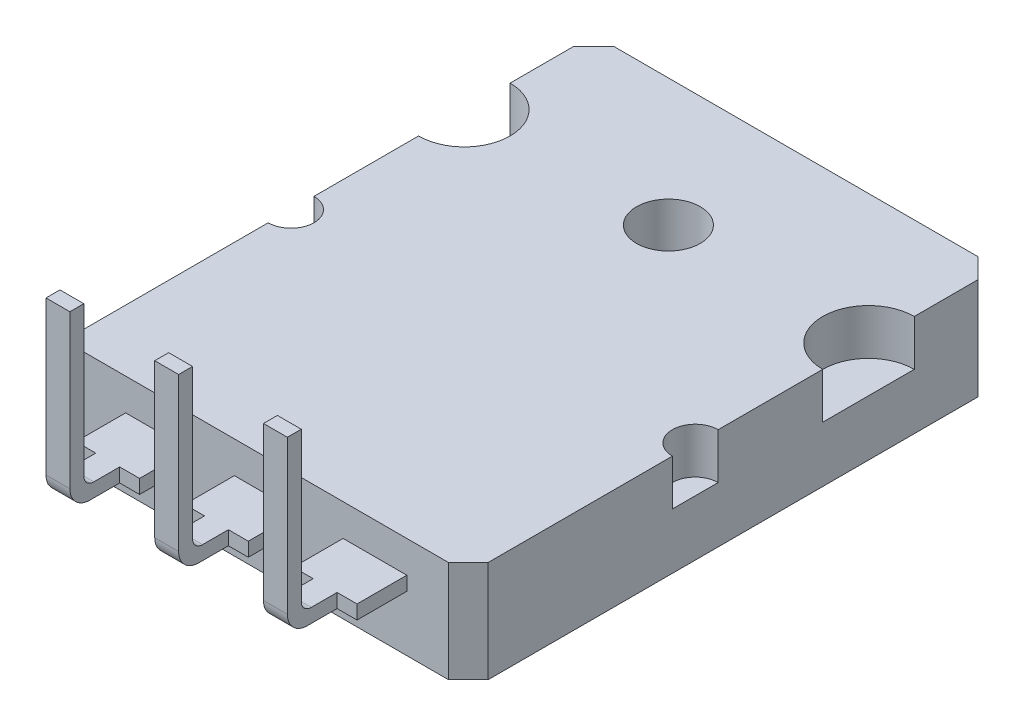
SolidWorks part; units mm, degrees
ref_plane "Спереди" through (0, 0, 0) normal (0, 0, 1) x (1, 0, 0)
ref_plane "Сверху" through (0, 0, 0) normal (0, 1, 0) x (1, 0, 0)
ref_plane "Справа" through (0, 0, 0) normal (1, 0, 0) x (0, 0, -1)
sketch "Эскиз1" plane through (0, 0, 0) normal (0, 1, 0) x (1, 0, 0)
  line L0 (10.15, 6.9) -> (-10.15, 6.9) construction
  line L1 (9.15, -13.3) -> (-9.15, -13.3)
  line L2 (10.15, -12.3) -> (10.15, 12.3)
  line L3 (9.15, 13.3) -> (-9.15, 13.3)
  line L4 (-10.15, -12.3) -> (-10.15, 12.3)
  line L5 (10.15, -13.3) -> (-10.15, 13.3) construction
  line L6 (10.15, 13.3) -> (-10.15, -13.3) construction
  line L7 (10.15, 6.8) -> (-10.15, 6.8) construction
  line L8 (10.15, 13.3) -> (-10.15, 13.3) construction
  line L9 (-9.15, 13.3) -> (-10.15, 12.3)
  line L10 (10.15, 12.3) -> (9.15, 13.3)
  line L11 (10.15, -12.3) -> (9.15, -13.3)
  line L12 (-9.15, -13.3) -> (-10.15, -12.3)
  line L13 (10.15, -1.9) -> (-10.15, -1.9) construction
  line L14 (3.861, -15.8) -> (4.861, -15.8)
  line L15 (0, -13.3) -> (0, -15.8) construction
  line L16 (-5.461, -13.3) -> (-5.461, -15.8) construction
  line L17 (5.461, -13.3) -> (5.461, -15.8) construction
  line L18 (-7.061, -13.3) -> (-7.061, -15.8)
  line L19 (-1.6, -13.3) -> (-1.6, -15.8)
  line L20 (3.861, -13.3) -> (3.861, -15.8)
  line L21 (-3.861, -13.3) -> (-3.861, -15.8)
  line L22 (1.6, -13.3) -> (1.6, -15.8)
  line L23 (7.061, -13.3) -> (7.061, -15.8)
  line L24 (-5.461, -15.8) -> (-5.461, -18.3) construction
  line L25 (-5.461, -18.3) -> (5.461, -18.3) construction
  line L26 (5.461, -18.3) -> (5.461, -15.8) construction
  line L27 (0, -15.8) -> (0, -18.3) construction
  line L28 (-6.061, -15.8) -> (-6.061, -18.3)
  line L29 (-0.6, -15.8) -> (-0.6, -18.3)
  line L30 (6.061, -18.3) -> (6.061, -15.8)
  line L31 (-4.861, -15.8) -> (-4.861, -18.3)
  line L32 (0.6, -15.8) -> (0.6, -18.3)
  line L33 (4.861, -18.3) -> (4.861, -15.8)
  line L34 (-6.061, -15.8) -> (-7.061, -15.8)
  line L35 (-4.861, -15.8) -> (-3.861, -15.8)
  line L36 (-1.6, -15.8) -> (-0.6, -15.8)
  line L37 (0.6, -15.8) -> (1.6, -15.8)
  line L38 (6.061, -15.8) -> (7.061, -15.8)
  line L39 (-6.061, -18.3) -> (-4.861, -18.3)
  line L40 (-0.6, -18.3) -> (0.6, -18.3)
  line L41 (4.861, -18.3) -> (6.061, -18.3)
  circle A0 centre (0, 6.9) radius 1.6
  circle A1 centre (0, 6.9) radius 3.65
  arc A2 (-10.15, 4.5) -> (-10.15, 9.1) centre (-10.15, 6.8) ccw
  arc A3 (10.15, 9.1) -> (10.15, 4.5) centre (10.15, 6.8) ccw
  arc A4 (-10.15, -3.05) -> (-10.15, -0.75) centre (-10.15, -1.9) ccw
  arc A5 (10.15, -0.75) -> (10.15, -3.05) centre (10.15, -1.9) ccw
  point P0 (0, 0)
  dimension "D4" = 3.2
  dimension "D5" = 7.3
  dimension "D7" = 4.6
  dimension "D9" = 2.3
  dimension "D1" = 20.3
  dimension "D2" = 26.6
  dimension "D19" = 5
  dimension "D10" = 2.5
  dimension "D3" = 6.4
  dimension "D6" = 6.5
  dimension "D8" = 8.7
  dimension "D15" = 5.461
  dimension "D16" = 5.461
  dimension "D17" = 1.6
  dimension "D18" = 1.6
  dimension "D20" = 0.6
  dimension "D21" = 0.6
extrude "Бобышка-Вытянуть1" add sketch "Эскиз1" against normal blind 2.8 contours A5 L2 A3 L10 L3 L9 L4 A2 A4 L12 L1 L11 A1 | L4 A2 | L4 A4 | L2 A3 | L2 A5 | A1 A0 region at (0, 0, 0.8287) region at (9.6619, 0, 1.9) region at (9.1738, 0, -6.8) region at (-9.6619, 0, 1.9) region at (-9.1738, 0, -6.8) region at (-3.5468, 0, -6.9)
extrude "Бобышка-Вытянуть2" add sketch "Эскиз1<3>" along normal blind 2.3 contours A5 L2 A3 L10 L3 L9 L4 A2 A4 L12 L1 L11 A1 | A1 A0 region at (0, 0, 0.8287) region at (-3.5468, 0, -6.9)
sketch "Эскиз1<3>" plane through (0, 0, 0) normal (0, 1, 0) x (1, 0, 0) same geometry as "Эскиз1"
extrude "Бобышка-Вытянуть3" add sketch "Эскиз1<4>" along normal blind 0.7 contours L28 L39 L31 L35 L21 L1 L18 L34 | L29 L40 L32 L37 L22 L1 L19 L36 | L33 L41 L30 L38 L23 L1 L20 L14 region at (5.461, 0, 15.2318) region at (0, 0, 15.2318) region at (-5.461, 0, 15.2318)
sketch "Эскиз1<4>" plane through (0, 0, 0) normal (0, 1, 0) x (1, 0, 0) same geometry as "Эскиз1"
sketch "Эскиз2" plane through (0, 0.7, 0) normal (0, 1, 0) x (1, 0, 0)
  line L0 (-4.861, -15.8) -> (-4.861, -18.3) construction
  line L1 (-6.061, -18.3) -> (-4.861, -18.3)
  line L2 (-6.061, -18.3) -> (-6.061, -17.6)
  line L3 (-6.061, -17.6) -> (-4.861, -17.6)
  line L4 (-4.861, -18.3) -> (-4.861, -17.6)
  line L5 (-6.061, -18.3) -> (-4.861, -17.6) construction
  line L6 (-6.061, -17.6) -> (-4.861, -18.3) construction
  line L7 (0.6, -15.8) -> (0.6, -18.3) construction
  line L8 (-0.6, -18.3) -> (0.6, -18.3)
  line L9 (-0.6, -18.3) -> (-0.6, -17.6)
  line L10 (-0.6, -17.6) -> (0.6, -17.6)
  line L11 (0.6, -18.3) -> (0.6, -17.6)
  line L12 (-0.6, -18.3) -> (0.6, -17.6) construction
  line L13 (-0.6, -17.6) -> (0.6, -18.3) construction
  line L14 (6.061, -18.3) -> (6.061, -15.8) construction
  line L15 (4.861, -18.3) -> (6.061, -18.3)
  line L16 (4.861, -18.3) -> (4.861, -17.6)
  line L17 (4.861, -17.6) -> (6.061, -17.6)
  line L18 (6.061, -18.3) -> (6.061, -17.6)
  line L19 (4.861, -18.3) -> (6.061, -17.6) construction
  line L20 (4.861, -17.6) -> (6.061, -18.3) construction
  point P4 (-5.461, -17.95)
  point P12 (0, -17.95)
  point P20 (5.461, -17.95)
  dimension "D1" = 0.7
extrude "Бобышка-Вытянуть4" add sketch "Эскиз2" along normal blind 8
fillet "Скругление1" radius 0.5 3 edges at (-5.461, 0.7, 17.6) (0, 0.7, 17.6) (5.461, 0.7, 17.6)
fillet "Скругление2" radius 1 3 edges at (-5.461, 0, 18.3) (0, 0, 18.3) (5.461, 0, 18.3)
